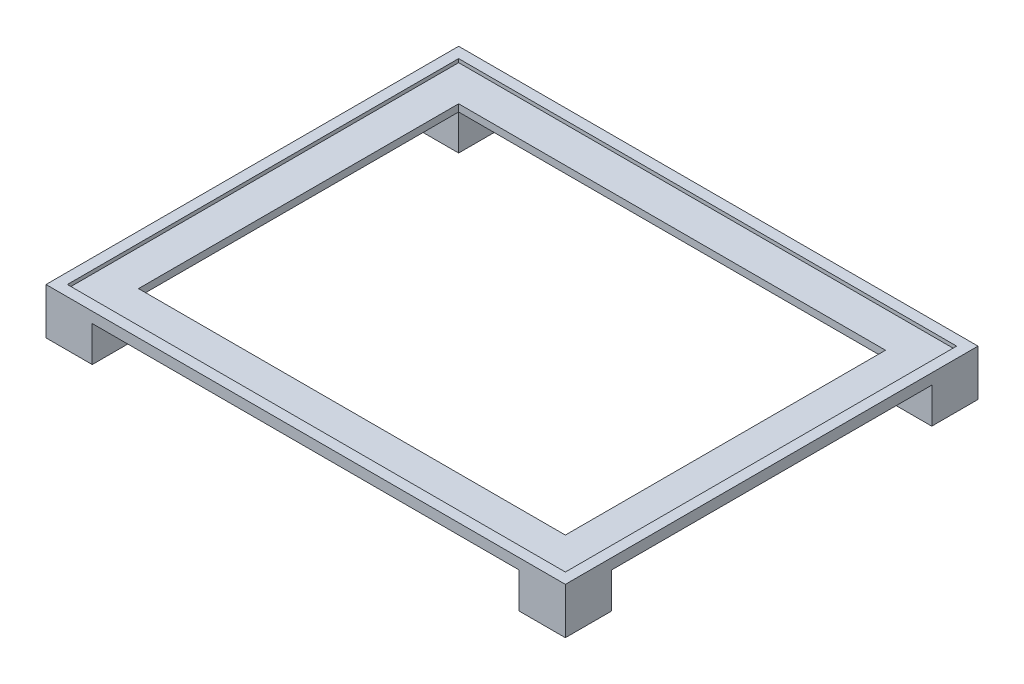
SolidWorks part; units mm, degrees
ref_plane "Front Plane" through (0, 0, 0) normal (0, 0, 1) x (1, 0, 0)
ref_plane "Top Plane" through (0, 0, 0) normal (0, 1, 0) x (1, 0, 0)
ref_plane "Right Plane" through (0, 0, 0) normal (1, 0, 0) x (0, 0, -1)
sketch "Sketch1" plane through (0, 0, 0) normal (0, 1, 0) x (1, 0, 0)
  line L1 (73, 58) -> (-73, 58)
  line L2 (73, 58) -> (73, -58)
  line L3 (73, -58) -> (-73, -58)
  line L4 (-73, 58) -> (-73, -58)
  line L5 (73, 58) -> (-73, -58) construction
  line L6 (73, -58) -> (-73, 58) construction
  line L7 (70, 55) -> (-70, 55)
  line L8 (70, 55) -> (70, -55)
  line L9 (70, -55) -> (-70, -55)
  line L10 (-70, 55) -> (-70, -55)
  line L11 (70, 55) -> (-70, -55) construction
  line L12 (70, -55) -> (-70, 55) construction
  line L13 (60, 45) -> (-60, 45)
  line L14 (60, 45) -> (60, -45)
  line L15 (60, -45) -> (-60, -45)
  line L16 (-60, 45) -> (-60, -45)
  line L17 (60, 45) -> (-60, -45) construction
  line L18 (60, -45) -> (-60, 45) construction
  point P0 (0, 0)
  point P6 (0, 0)
  point P11 (0, 0)
  dimension "D1" = 116
  dimension "D2" = 146
  dimension "D3" = 140
  dimension "D4" = 110
  dimension "D5" = 90
  dimension "D6" = 120
extrude "Dinding" add sketch "Sketch1" along normal blind 3 contours L1 L4 L3 L2 L10 L7 L8 L9 region at (71.1353, 0, 0)
extrude "Landsite" add sketch "Sketch1<4>" along normal blind 2 contours L7 L10 L9 L8 L16 L13 L14 L15 region at (68.2196, 0, 0)
sketch "Sketch1<4>" plane through (0, 0, 0) normal (0, 1, 0) x (1, 0, 0) same geometry as "Sketch1"
sketch "Sketch2" plane through (0, 0, 0) normal (0, -1, 0) x (1, 0, 0)
  line L6 (-73, 58) -> (-60, 58)
  line L13 (-73, -58) -> (-60, -58)
  line L14 (-73, -58) -> (-73, -45)
  line L20 (73, 58) -> (60, 58)
  line L21 (73, 58) -> (73, 45)
  line L22 (-73, 58) -> (-73, 45)
  line L27 (73, -58) -> (60, -58)
  line L28 (73, -58) -> (73, -45)
  line L29 (-73, 45) -> (-60, 45)
  line L30 (-60, 58) -> (-60, 45)
  line L31 (-73, -45) -> (-60, -45)
  line L32 (-60, -58) -> (-60, -45)
  line L33 (73, -45) -> (60, -45)
  line L34 (60, -58) -> (60, -45)
  line L35 (73, 45) -> (60, 45)
  line L36 (60, 58) -> (60, 45)
  point P0 (-68.5, 54.25)
  line M17 (-73, -58) -> (73, -58)
  line M18 (73, -58) -> (73, 58)
  line M19 (73, 58) -> (-73, 58)
  line M20 (-73, 58) -> (-73, -58)
extrude "Kaki" add sketch "Sketch2" along normal blind 10 contours L30 L29 M19 M20 | L32 L31 M17 M20 | L34 L33 M17 M18 | L36 L35 M19 M18 region at (-66.5, 0, 51.5) region at (66.5, 0, 51.5) region at (-66.5, 0, -51.5) region at (66.5, 0, -51.5)
